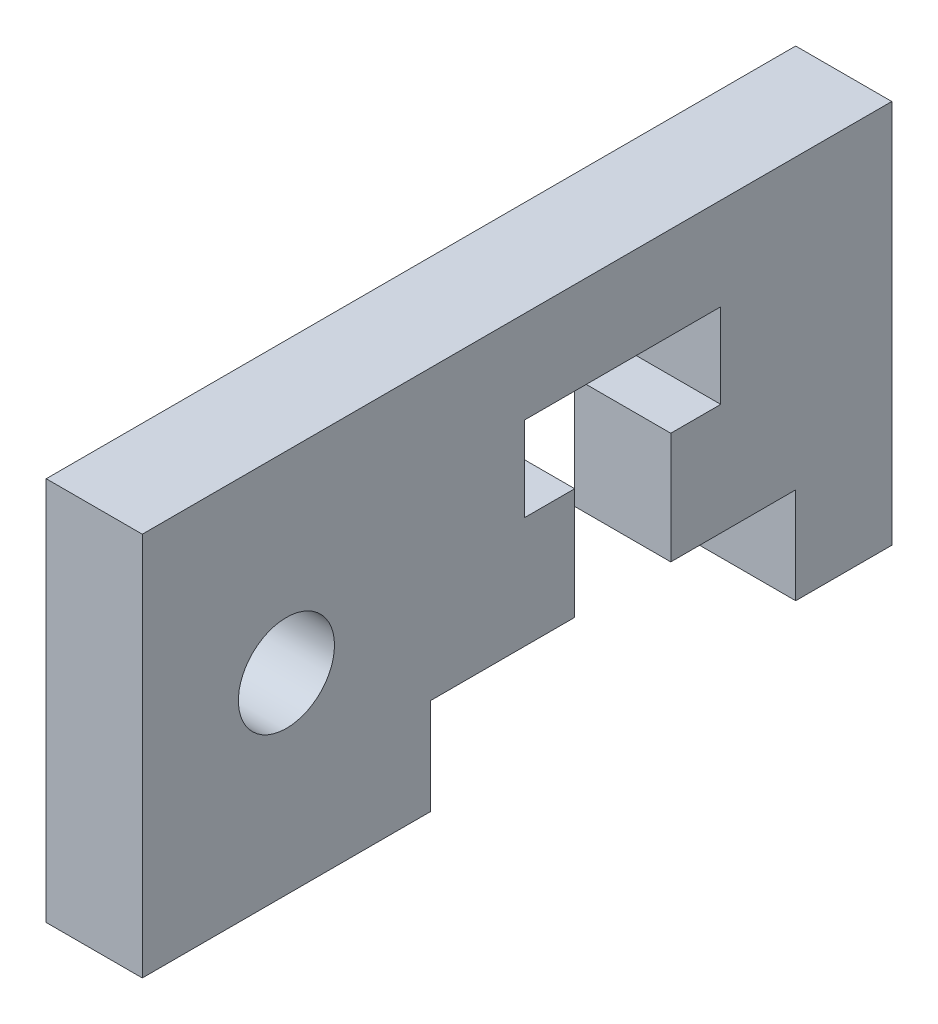
SolidWorks part; units mm, degrees
ref_plane "Front Plane" through (0, 0, 0) normal (0, 0, 1) x (1, 0, 0)
ref_plane "Top Plane" through (0, 0, 0) normal (0, 1, 0) x (1, 0, 0)
ref_plane "Right Plane" through (0, 0, 0) normal (1, 0, 0) x (0, 0, -1)
sketch "Sketch2" plane through (0, 0, 0) normal (1, 0, 0) x (0, 0, -1)
  line L0 (-4.7625, 6.35) -> (-4.7625, -6.35)
  line L1 (-4.7625, -6.35) -> (4.7625, -6.35)
  line L2 (4.7625, -6.35) -> (4.7625, -3.175)
  line L3 (12.7, -3.175) -> (16.8275, -3.175)
  line L4 (20.0025, -6.35) -> (20.0025, 6.35)
  line L5 (20.0025, 6.35) -> (-4.7625, 6.35)
  line L6 (-19.474, 0) -> (-4.2216, 0) construction
  line L7 (12.7, -3.175) -> (12.7, 0.508)
  line L8 (12.7, 0.508) -> (14.351, 0.508)
  line L9 (14.351, 0.508) -> (14.351, 3.302)
  line L10 (14.351, 3.302) -> (7.874, 3.302)
  line L11 (7.874, 3.302) -> (7.874, 0.508)
  line L12 (7.874, 0.508) -> (9.525, 0.508)
  line L13 (9.525, 0.508) -> (9.525, -3.175)
  line L14 (9.525, -3.175) -> (4.7625, -3.175)
  line L15 (11.1125, 0.9915) -> (11.1125, -22.7495) construction
  line L16 (16.8275, -3.175) -> (16.8275, -6.35)
  line L17 (16.8275, -6.35) -> (20.0025, -6.35)
  circle A0 centre (0, 0) radius 1.5875
  point P10 (-4.7625, 0)
  point P21 (11.1125, 3.302)
  dimension "D2" = 3.175
  dimension "D1" = 12.7
  dimension "D3" = 3.175
  dimension "D4" = 9.525
  dimension "D5" = 4.7625
  dimension "D6" = 24.765
  dimension "D7" = 6.477
  dimension "D8" = 3.175
  dimension "D9" = 8.89
  dimension "D10" = 6.477
  dimension "D11" = 2.794
  dimension "D12" = 3.175
extrude "Boss-Extrude1" add sketch "Sketch2" along normal blind 1.5875 and the other way blind 1.5875
